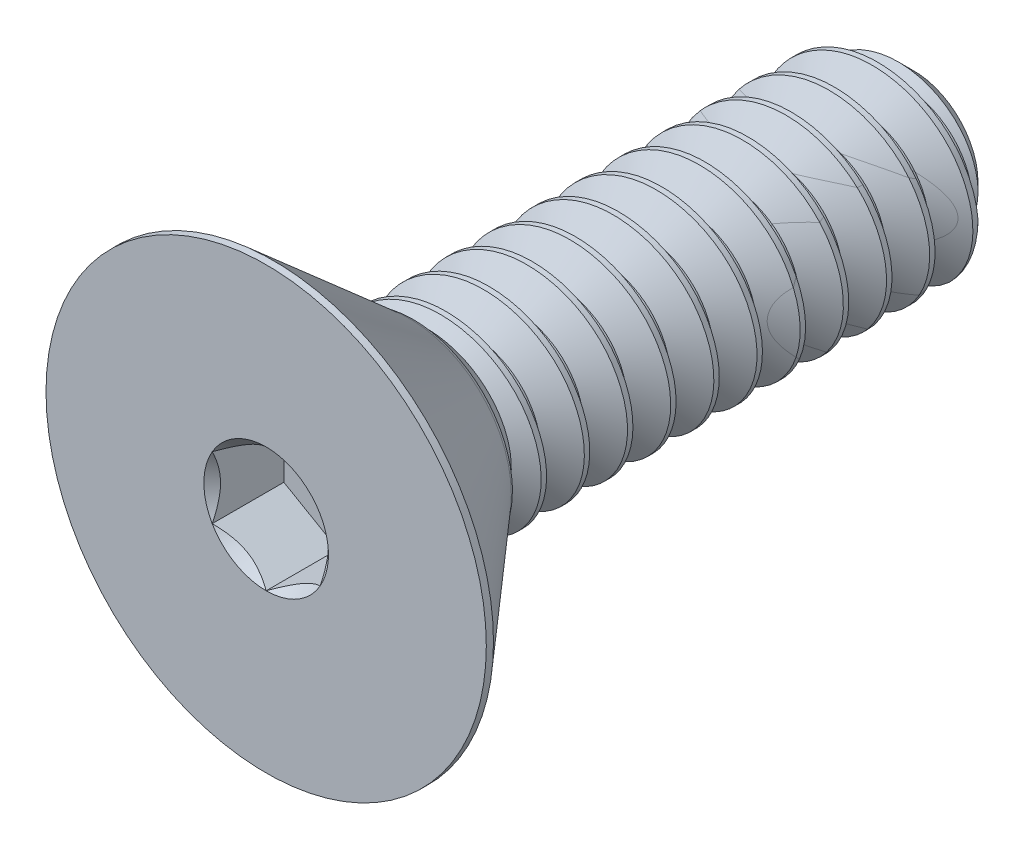
SolidWorks part; units mm, degrees
ref_plane "Front Plane" through (0, 0, 0) normal (0, 0, 1) x (1, 0, 0)
ref_plane "Top Plane" through (0, 0, 0) normal (0, 1, 0) x (1, 0, 0)
ref_plane "Right Plane" through (0, 0, 0) normal (1, 0, 0) x (0, 0, -1)
sketch "Sketch1" plane through (0, 0, 0) normal (1, 0, 0) x (0, 0, -1)
  line L0 (-4.7625, 0) -> (4.7625, 0) construction
  line L1 (-4.7625, 0) -> (-4.7625, 3.2385)
  line L2 (-2.5679, 1.4224) -> (-4.6571, 3.2385)
  line L3 (-2.5679, 1.4224) -> (4.7625, 1.4224)
  line L4 (4.7625, 1.4224) -> (4.7625, 0)
  line L5 (-4.7625, -3.2385) -> (-4.6571, -3.2385) construction
  line L6 (-4.7625, 0) -> (-4.7625, -3.2385) construction
  line L7 (-4.7625, 3.2385) -> (-4.6571, 3.2385)
  line L8 (-4.6571, -3.2385) -> (-2.5679, -1.4224) construction
  line L9 (4.7228, 1.4911) -> (5.0403, 0.9412) construction
  line L10 (5.0403, 0.9412) -> (5.3578, 1.4911) construction
  line L11 (5.3578, 1.4911) -> (4.7228, 1.4911) construction
  line L12 (4.7625, 1.4224) -> (5.3181, 1.4224) construction
  line L13 (5.0403, 1.4911) -> (5.0403, 1.4224) construction
  line L14 (5.0403, 1.4224) -> (5.0403, 1.01) construction
  line L15 (5.0403, 1.01) -> (5.0403, 0.9412) construction
  line L16 (5.0006, 1.01) -> (5.08, 1.01)
  line L17 (4.7427, 1.4568) -> (5.338, 1.4568)
  line L18 (5.08, 1.01) -> (5.338, 1.4568)
  line L19 (5.0006, 1.01) -> (4.7427, 1.4568)
  point P12 (-2.6543, 1.4224)
  point P22 (5.0403, 1.4568)
  point P23 (3.175, -1.4224)
  point P28 (-2.6543, -1.4224)
  dimension "Head Diameter" = 6.477
  dimension "Length" = 9.525
  dimension "Screw Size Decimal Equivalent" = 2.8448
  dimension "Countersink Angle" = 82
  dimension "Pitch" = 0.635
  dimension "D2" = 0.0794
  dimension "D1" = 1.8824
  dimension "Head Height" = 2.1082
  dimension "D3" = 0.1054
  dimension "D4" = 1.5875
sketch "Sketch2" plane through (0, 0, 0) normal (0, 0, 1) x (1, 0, 0)
  line L1 (0, 0.9165) -> (-0.7937, 0.4583)
  line L2 (-0.7937, 0.4583) -> (-0.7937, -0.4583)
  line L3 (-0.7937, -0.4583) -> (0, -0.9165)
  line L4 (0, -0.9165) -> (0.7938, -0.4583)
  line L5 (0.7938, -0.4583) -> (0.7938, 0.4583)
  line L6 (0.7938, 0.4583) -> (0, 0.9165)
  circle A0 centre (0, 0) radius 0.7937 construction
  circle A1 centre (0, 0) radius 3.2385
  dimension "D1" = 6.477
  dimension "Drive Size" = 1.5875
sketch "Sketch3" plane through (0, 0, 0) normal (1, 0, 0) x (0, 0, -1)
  line L0 (-4.7625, 0) -> (-4.7625, 3.2385) construction
  line L1 (-4.7625, 3.2385) -> (-4.6571, 3.2385) construction
  line L2 (-2.5679, 1.4224) -> (-4.6571, 3.2385) construction
  line L3 (-2.5679, 1.4224) -> (4.7625, 1.4224) construction
  line L4 (4.7625, 1.4224) -> (4.7625, 0) construction
  line L5 (-4.7625, 0) -> (-4.7625, 3.2385)
  line L6 (-4.7625, 3.2385) -> (-4.6571, 3.2385)
  line L7 (-2.5679, 1.4224) -> (-4.6571, 3.2385)
  line L8 (-2.5679, 1.4224) -> (4.7625, 1.4224)
  line L9 (4.7625, 1.4224) -> (4.7625, 0)
  line L10 (-4.7625, 0) -> (4.7625, 0)
revolve "Revolve1" add sketch "Sketch3" angle 360 about L0
fillet "Fillet1" radius 0.2845 1 edges at (1.4224, 0, 2.5679)
chamfer "Chamfer1" distance 0.4763 angle 45 1 edges at (1.4224, 0, -4.7625)
sketch "Sketch4" plane through (0, 0, 4.7625) normal (0, 0, 1) x (1, 0, 0)
  line L0 (0.7938, 0.4583) -> (0, 0.9165) construction
  line L1 (0.7938, -0.4583) -> (0.7938, 0.4583) construction
  line L2 (0, -0.9165) -> (0.7938, -0.4583) construction
  line L3 (-0.7937, -0.4583) -> (0, -0.9165) construction
  line L4 (-0.7937, 0.4583) -> (-0.7937, -0.4583) construction
  line L5 (0, 0.9165) -> (-0.7937, 0.4583) construction
  line L6 (0.7938, 0.4583) -> (0, 0.9165)
  line L7 (0.7938, -0.4583) -> (0.7938, 0.4583)
  line L8 (0, -0.9165) -> (0.7938, -0.4583)
  line L9 (-0.7937, -0.4583) -> (0, -0.9165)
  line L10 (-0.7937, 0.4583) -> (-0.7937, -0.4583)
  line L11 (0, 0.9165) -> (-0.7937, 0.4583)
extrude "Cut-Extrude1" cut sketch "Sketch4" against normal blind 1.0541
sketch "Sketch5" plane through (0, 0, 4.7625) normal (0, 0, 1) x (1, 0, 0)
  circle A0 centre (0, 0) radius 0.9165
extrude "Cut-Extrude3" cut sketch "Sketch5" against normal up to next (1.0541 mm away) draft 45
sketch "Sketch7" plane through (0, 0, -4.7625) normal (0, 0, -1) x (-1, 0, 0)
  circle A1 centre (0, 0) radius 1.4224
curve "Helix/Spiral1" pitch 0.635 height 10.16 turns 16
sketch "Sketch8" plane through (0, 0, 0) normal (1, 0, 0) x (0, 0, -1)
  line L0 (5.0006, 1.01) -> (5.08, 1.01) construction
  line L1 (5.0006, 1.01) -> (4.7427, 1.4568) construction
  line L2 (4.7427, 1.4568) -> (5.338, 1.4568) construction
  line L3 (5.08, 1.01) -> (5.338, 1.4568) construction
  line L4 (5.0006, 1.01) -> (5.08, 1.01)
  line L5 (5.0006, 1.01) -> (4.7427, 1.4568)
  line L6 (4.7427, 1.4568) -> (5.338, 1.4568)
  line L7 (5.08, 1.01) -> (5.338, 1.4568)
ref_plane "Plane1" through (0, 0, 2.6543) normal (0, 0, 1) x (1, 0, 0)
split "Split1" trim tools "Plane1" bodies to split 106 resulting bodies 109 110
sweep "Cut-Sweep1" cut profiles "Sketch8" path "Helix/Spiral1"
sketch "Nylon Patch" plane through (0, 0, 0) normal (1, 0, 0) x (0, 0, -1)
  line L0 (-4.7625, 0) -> (4.7625, 0) construction
  line L3 (4.7625, 1.4224) -> (4.7625, 0) construction
  ellipse E0 centre (2.8098, 0) end of major axis (4.1275, 0) minor radius 0.9412
  dimension "D1" = 2.6354
  dimension "D2" = 0.635
sketch "Sketch9" plane through (0, 0, 2.6543) normal (0, 0, 1) x (1, 0, 0)
  circle A1 centre (0, 0) radius 1.4975
  circle A3 centre (0, 0) radius 1.4975
  dimension "D1" = 0
extrude "Boss-Extrude1" add sketch "Sketch9" against normal up to body (7.4168 mm away) draft 45 separate body
split "Split2" trim tools "Nylon Patch" bodies to split 112 resulting bodies 115 116
equation "\"D2@Sketch1\" = \"Pitch@Sketch1\" / 8"
equation "\"D1@Fillet1\"=\"Screw Size Decimal Equivalent@Sketch1\"*0.1"
equation "\"D1@Chamfer1\" = \"Pitch@Sketch1\" * 0.75"
equation "\"D1@Cut-Extrude1\"=\"Head Height@Sketch1\"*0.5"
equation "\"D4@Helix/Spiral1\"=\"Pitch@Sketch1\""
equation "\"D3@Helix/Spiral1\"=\"Length@Sketch1\"+\"Pitch@Sketch1\""
equation "\"D1@Nylon Patch\" = \"D1@Sketch1\" * 1.4"
equation "\"D2@Nylon Patch\" = \"Pitch@Sketch1\""
equation "\"D3@Sketch1\"=\"Head Height@Sketch1\"*0.05"
equation "\"D4@Sketch1\"=\"Pitch@Sketch1\"*2.5"
